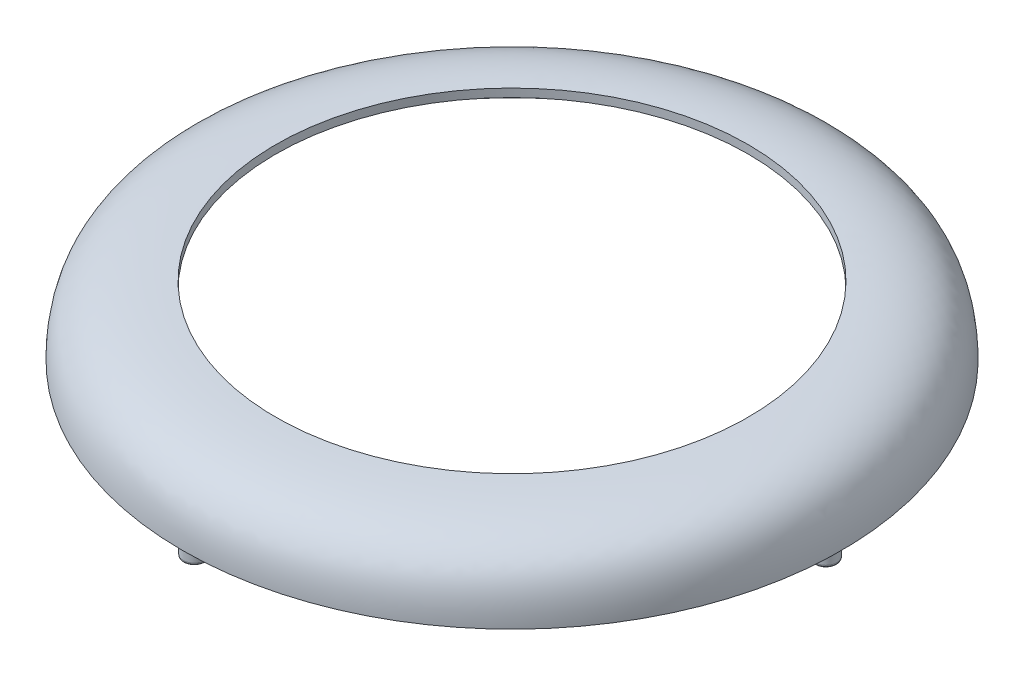
SolidWorks part; units mm, degrees
ref_plane "Front Plane" through (0, 0, 0) normal (0, 0, 1) x (1, 0, 0)
ref_plane "Top Plane" through (0, 0, 0) normal (0, 1, 0) x (1, 0, 0)
ref_plane "Right Plane" through (0, 0, 0) normal (1, 0, 0) x (0, 0, -1)
sketch "Sketch1" plane through (0, 0, 0) normal (0, 0, 1) x (1, 0, 0)
  line L0 (0, 0) -> (0, 267.6224) construction
  line L2 (120, 13.6989) -> (120, -13.6989) construction
  line L3 (120, 0) -> (117, 0)
  line L4 (86, 22) -> (86, 25)
  spline S0 degree 3 poles (120, 0) (120, 17.1237) (112.5963, 25) (86, 25) knots 0 0 0 0 1 1 1 1
  spline S1 degree 1 poles (117, 0) (86, 22) knots 0 0 1 1 construction
  spline S2 degree 3 poles (117, 0) (117, 0.4975) (116.9863, 1.5078) (116.9021, 3.4046) (116.6879, 5.6272) (116.2502, 8.028) (115.4217, 10.889) (113.9297, 13.8467) (111.3069, 16.6582) (108.1272, 18.5698) (104.821, 19.8199) (101.9393, 20.6035) (98.6363, 21.2228) (94.9025, 21.6699) (91.4107, 21.8948) (88.4074, 21.985) (86.7931, 22) (86, 22) knots 0 0 0 0 0.03125 0.0625 0.125 0.1875 0.25 0.375 0.5 0.625 0.6875 0.75 0.8125 0.875 0.9375 0.96875 1 1 1 1
  dimension "D1" = 172
  dimension "D2" = 240
  dimension "D3" = 25
  dimension "D4" = 3
revolve "Revolve1" add sketch "Sketch1" angle 360 about L0
sketch "Sketch2" plane through (0, 0, 0) normal (0, -1, 0) x (-1, 0, 0)
  circle A0 centre (-0.7045, 114.9978) radius 4
  circle A2 centre (0, 0) radius 120 construction
  point P2 (-0.6952, 113.4809)
  dimension "D1" = 8
  dimension "D2" = 115
extrude "Boss-Extrude1" add sketch "Sketch2" against normal up to next and the other way blind 5
fillet "Fillet1" radius 1 1 edges at (0.7045, -5, -118.9978)
pattern_circular "CirPattern1" count 4 over 360 about axis through (0, 0, 0) along (0, -1, 0) of "Fillet1", "Boss-Extrude1"
